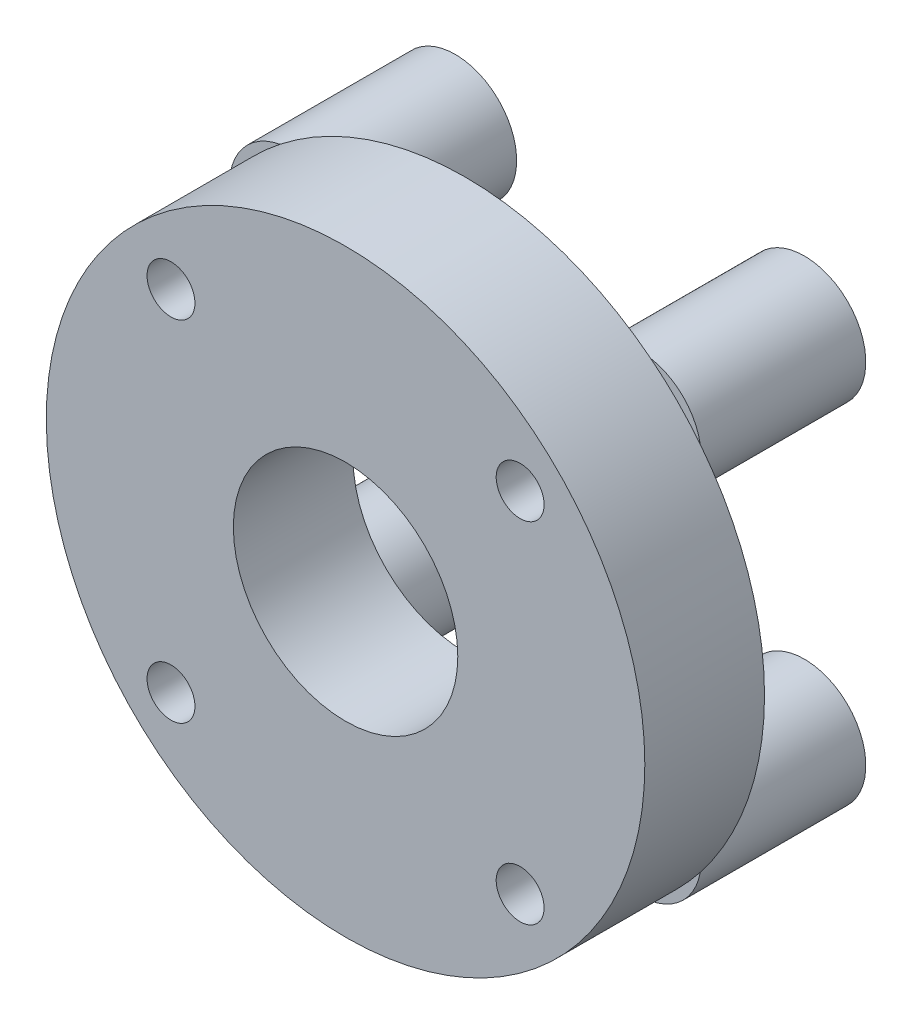
SolidWorks part; units mm, degrees
material "ABS"
ref_plane "Front Plane" through (0, 0, 0) normal (0, 0, 1) x (1, 0, 0)
ref_plane "Top Plane" through (0, 0, 0) normal (0, 1, 0) x (1, 0, 0)
ref_plane "Right Plane" through (0, 0, 0) normal (1, 0, 0) x (0, 0, -1)
ref_plane "Output Plane" through (0, 0, 15) normal (0, 0, -1) x (-1, 0, 0)
sketch "CYC Output Sketch" plane through (0, 0, 15) normal (0, 0, 1) x (1, 0, 0)
  line L1 (11.6673, 11.6673) -> (-11.6673, 11.6673) construction
  line L2 (-11.6673, 11.6673) -> (-11.6673, -11.6673) construction
  line L3 (-11.6673, -11.6673) -> (11.6673, -11.6673) construction
  line L4 (11.6673, -11.6673) -> (11.6673, 11.6673) construction
  circle A0 centre (0, 0) radius 16.5 construction
  point P1 (0, 0)
sketch "Sketch3" plane through (0, 0, 15) normal (0, 0, -1) x (-1, 0, 0)
  circle A0 centre (-11.6673, 11.6673) radius 4
  circle A1 centre (11.6673, 11.6673) radius 4
  circle A2 centre (11.6673, -11.6673) radius 4
  circle A3 centre (-11.6673, -11.6673) radius 4
  dimension "D1" = 8
extrude "Boss-Extrude1" add sketch "Sketch3" along normal blind 11
sketch "Sketch6" plane through (0, 0, 15) normal (0, 0, 1) x (1, 0, 0)
  arc A0 (10.6823, 16.9082) -> (-16.9082, 10.6823) centre (0, 0) ccw
  arc A18 (16.9082, -10.6823) -> (10.6823, 16.9082) centre (0, 0) ccw
  arc A19 (-10.6823, -16.9082) -> (16.9082, -10.6823) centre (0, 0) ccw
  arc A20 (-16.9082, 10.6823) -> (-10.6823, -16.9082) centre (0, 0) ccw
  circle A23 centre (0, 0) radius 7.5
  dimension "D2" = 40
  dimension "D1" = 15
extrude "Boss-Extrude6" add sketch "Sketch6" along normal blind 8 contours A23 | A0 A20 A19 A18 region at (0, 0, 15)
sketch "Sketch8" plane through (0, 0, 23) normal (0, 0, 1) x (1, 0, 0)
  line L0 (0, 0) -> (11.6673, 11.6673) construction
  line L1 (0, 0) -> (16.5, 0) construction
  circle A0 centre (0, 0) radius 16.5 construction
  circle A1 centre (11.6673, 11.6673) radius 1.6
  circle A2 centre (11.6673, -11.6673) radius 1.6
  circle A3 centre (-11.6673, -11.6673) radius 1.6
  circle A4 centre (-11.6673, 11.6673) radius 1.6
  point P16 (0, 0)
  dimension "D1" = 33
  dimension "D2" = 45
  dimension "D3" = 3.2
  dimension "D4" = 4
extrude "Cut-Extrude1" cut sketch "Sketch8" against normal through all
sketch "Sketch9" plane through (0, 0, 4) normal (0, 0, 1) x (1, 0, 0)
  circle A0 centre (11.6673, 11.6673) radius 3
  circle A1 centre (11.6673, -11.6673) radius 3
  circle A2 centre (-11.6673, -11.6673) radius 3
  circle A3 centre (-11.6673, 11.6673) radius 3
  point P12 (0, 0)
  dimension "D1" = 6
  dimension "D2" = 4
extrude "Cut-Extrude2" cut sketch "Sketch9" along normal blind 3 from surface starting at face at (13.2673, 11.6673, 4)
sketch "Sketch10" plane through (0, 0, 4) normal (0, 0, -1) x (-1, 0, 0)
  circle A0 centre (11.6673, 11.6673) radius 4.1
  circle A1 centre (11.6673, 11.6673) radius 4
  circle A2 centre (11.6673, -11.6673) radius 4
  circle A3 centre (11.6673, -11.6673) radius 4.1
  circle A4 centre (-11.6673, -11.6673) radius 4
  circle A5 centre (-11.6673, -11.6673) radius 4.1
  circle A6 centre (-11.6673, 11.6673) radius 4
  circle A7 centre (-11.6673, 11.6673) radius 4.1
  point P16 (0, 0)
  dimension "D1" = 8
  dimension "D2" = 8.2
  dimension "D3" = 4
extrude "Boss-Extrude8" add sketch "Sketch10" against normal blind 11
equation "\"RingPinShaft\"= 5.05"
equation "\"CenterBearingOut\"=32.00"
equation "\"RingPostIn\"=5.15"
equation "\"CamBearingOut\"=15.1"
equation "\"DiskOutputShaft\"=10.1"
equation "\"CenterShaft\"=25.2"
equation "\"Eccentricity\"=2"
equation "\"CycCamShaft\"=10.05"
equation "\"D2@Sketch6\"=\"OutputBearing\""
equation "\"OutputBearing\"=40"
